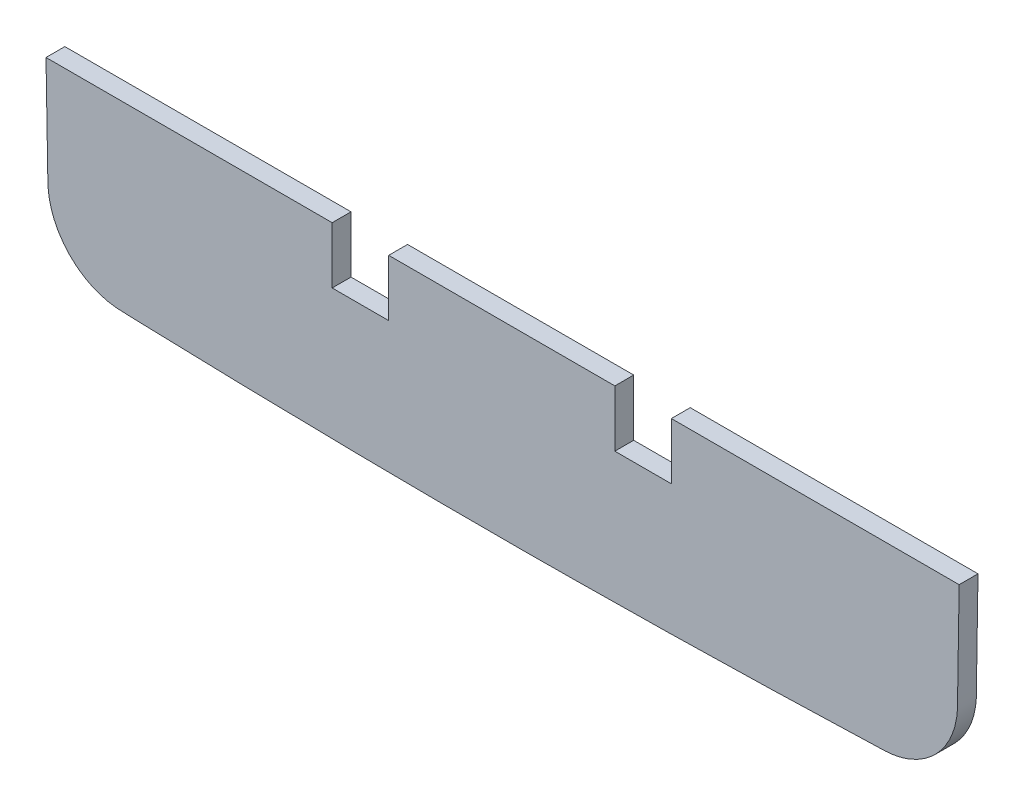
SolidWorks part; units mm, degrees
material "Balsa"
ref_plane "Front Plane" through (0, 0, 0) normal (0, 0, 1) x (1, 0, 0)
ref_plane "Top Plane" through (0, 0, 0) normal (0, 1, 0) x (1, 0, 0)
ref_plane "Right Plane" through (0, 0, 0) normal (1, 0, 0) x (0, 0, -1)
sketch "Sketch1" plane through (0, 0, 0) normal (0, 0, 1) x (1, 0, 0)
  line L0 (0, 0) -> (63.5, 0) construction
  line L1 (63.5, 0) -> (63.5, -63.8615) construction
  line L2 (63.5, 0) -> (63.5, 63.3303) construction
  line L3 (63.5, 0) -> (125.3812, 0) construction
  line L4 (1.8568, -38.4615) -> (125.1432, -38.4615)
  line L5 (48.26, -46.0815) -> (40.64, -38.4615) construction
  line L6 (78.74, -38.4615) -> (86.36, -38.4615)
  line L7 (78.74, -38.4615) -> (78.74, -46.0815)
  line L8 (78.74, -46.0815) -> (86.36, -46.0815)
  line L9 (86.36, -38.4615) -> (86.36, -46.0815)
  line L10 (78.74, -38.4615) -> (86.36, -46.0815) construction
  line L11 (78.74, -46.0815) -> (86.36, -38.4615) construction
  line L12 (48.26, -38.4615) -> (40.64, -46.0815) construction
  line L13 (40.64, -38.4615) -> (40.64, -46.0815)
  line L14 (48.26, -46.0815) -> (40.64, -46.0815)
  line L15 (48.26, -38.4615) -> (48.26, -46.0815)
  line L16 (48.26, -38.4615) -> (40.64, -38.4615)
  spline S0 degree 3 poles (54.6746, 63.3201) (72.3254, 63.3404) (81.6334, 63.261) (91.4786, 63.0757) (96.4012, 62.983) (101.4588, 62.8641) (106.6652, 62.7189) (109.2684, 62.6463) (111.9089, 62.5672) (114.589, 62.4817) (114.9241, 62.471) (115.2596, 62.4627) (115.9368, 62.4005) (116.2773, 62.3518) (116.6174, 62.2851) (117.2977, 62.1518) (117.9765, 61.9466) (119.2931, 61.385) (119.9309, 61.0284) (120.5286, 60.6045) (120.8274, 60.3925) (121.1162, 60.1638) (121.3925, 59.9193) (121.5306, 59.7971) (121.6656, 59.671) (121.8628, 59.4761) (121.9277, 59.4102) (122.0237, 59.3099) (122.0555, 59.2763) (122.1028, 59.2255) (122.1185, 59.2085) (122.142, 59.1829) (122.1498, 59.1744) (122.1615, 59.1615) (122.1654, 59.1573) (122.1732, 59.1487) (122.1779, 59.1435) (122.181, 59.1401) (122.9771, 58.2612) (123.6304, 57.2281) (124.5379, 55.0046) (124.7916, 53.8141) (124.8407, 52.6335) (124.8468, 52.4859) (124.8489, 52.3387) (124.8543, 52.0436) (124.8571, 51.8957) (124.8598, 51.7477) (124.8652, 51.4515) (124.8707, 51.1544) (124.8761, 50.8563) (124.8869, 50.2602) (124.8976, 49.66) (124.9083, 49.056) (124.9296, 47.8479) (124.9506, 46.624) (124.9711, 45.3844) (125.0123, 42.9053) (125.0517, 40.3631) (125.0888, 37.7579) (125.1074, 36.4553) (125.1253, 35.1369) (125.1426, 33.8028) (125.1513, 33.1357) (125.1598, 32.4647) (125.1681, 31.7898) (125.1722, 31.4523) (125.1763, 31.1138) (125.1804, 30.7744) (125.1824, 30.6047) (125.1844, 30.4347) (125.1875, 30.1794) (125.1885, 30.0942) (125.1899, 29.9664) (125.1904, 29.9237) (125.1912, 29.8598) (125.1914, 29.8384) (125.1918, 29.8064) (125.1919, 29.7958) (125.1921, 29.7798) (125.1922, 29.7744) (125.1923, 29.7638) (125.1924, 29.7566) (125.1924, 29.7531) (125.2344, 26.1435) (125.2782, 21.8295) (125.3138, 16.8106) (125.3316, 14.3012) (125.3473, 11.6156) (125.3591, 8.7538) (125.3651, 7.3229) (125.37, 5.848) (125.3738, 4.3291) (125.3757, 3.5696) (125.3773, 2.7992) (125.3786, 2.0177) (125.3793, 1.627) (125.3798, 1.2335) (125.3803, 0.8373) (125.3805, 0.6391) (125.3807, 0.4403) (125.381, 0.1411) (125.3811, 0.0412) (125.3813, -0.1089) (125.3813, -0.159) (125.3814, -0.2342) (125.3814, -0.2593) (125.3814, -0.2969) (125.3814, -0.3095) (125.3814, -0.3346) (125.3814, -0.3459) (125.3815, -0.3597) (125.3867, -7.4209) (125.3638, -13.4611) (125.3337, -18.4799) (125.3187, -20.9893) (125.3018, -23.2434) (125.2849, -25.2423) (125.2765, -26.2418) (125.2681, -27.1774) (125.2599, -28.0493) (125.2558, -28.4852) (125.2517, -28.9052) (125.2477, -29.3092) (125.2457, -29.5113) (125.2438, -29.7093) (125.2408, -30.0004) (125.2399, -30.0964) (125.2384, -30.239) (125.2379, -30.2862) (125.2372, -30.3568) (125.237, -30.3802) (125.2366, -30.4153) (125.2365, -30.427) (125.2363, -30.4445) (125.2362, -30.4503) (125.2362, -30.459) (125.2361, -30.4619) (125.2361, -30.4663) (125.2361, -30.4678) (125.236, -30.4707) (125.236, -30.4709) (125.236, -30.4736) (125.179, -36.029) (125.1091, -41.2841) (125.0327, -46.2395) (125.0136, -47.4783) (124.9941, -48.6984) (124.9743, -49.8998) (124.9644, -50.5005) (124.9544, -51.0965) (124.9443, -51.6878) (124.9393, -51.9835) (124.9342, -52.2779) (124.9291, -52.5713) (124.9266, -52.7179) (124.9247, -52.8642) (124.9129, -53.1574) (124.9038, -53.3041) (124.8916, -53.4507) (124.7938, -54.6239) (124.4947, -55.7922) (124.0038, -56.8717) (123.7584, -57.4114) (123.4662, -57.9292) (123.1347, -58.416) (122.969, -58.6594) (122.7933, -58.8951) (122.6087, -59.1219) (122.5164, -59.2354) (122.4219, -59.3466) (122.2769, -59.51) (122.228, -59.5638) (122.1539, -59.6438) (122.129, -59.6703) (122.0916, -59.7098) (122.0791, -59.7229) (122.0603, -59.7426) (122.054, -59.7491) (122.0446, -59.7589) (122.0414, -59.7621) (122.0351, -59.7687) (122.0329, -59.771) (122.0288, -59.7752) (120.9867, -60.8512) (119.7112, -61.6814) (118.3671, -62.1967) (117.6951, -62.4544) (117.0057, -62.6355) (116.3186, -62.7439) (115.975, -62.7981) (115.632, -62.8341) (115.2919, -62.8524) (115.1218, -62.8615) (114.9526, -62.866) (114.6141, -62.8777) (114.445, -62.8836) (114.276, -62.8894) (111.5731, -62.9828) (108.9135, -63.0695) (106.2945, -63.1494) (101.0567, -63.3091) (95.9813, -63.4414) (86.1268, -63.6511) (81.3478, -63.7286) (76.7076, -63.7803) (74.3874, -63.8062) (72.102, -63.8257) (69.8505, -63.8391) (68.7248, -63.8459) (67.6075, -63.8511) (65.3896, -63.8586) (64.2876, -63.8609) (63.1969, -63.8617) (54.4717, -63.8687) (45.2104, -63.7853) (35.3493, -63.5924) (30.4187, -63.496) (25.3375, -63.3725) (20.091, -63.222) (18.7794, -63.1844) (17.4574, -63.1451) (16.1247, -63.1042) (15.4584, -63.0837) (14.7894, -63.0628) (14.1177, -63.0415) (13.7818, -63.0309) (13.4453, -63.0201) (12.7708, -62.9984) (12.4333, -62.9897) (12.0943, -62.9762) (10.7385, -62.922) (9.3303, -62.5848) (8.0249, -61.938) (7.3723, -61.6146) (6.7455, -61.216) (6.1651, -60.7512) (5.8749, -60.5187) (5.5963, -60.2697) (5.332, -60.0053) (5.1999, -59.8731) (5.0713, -59.737) (4.8841, -59.5275) (4.8226, -59.4568) (4.7319, -59.3494) (4.7019, -59.3134) (4.6572, -59.2591) (4.6424, -59.2409) (4.6203, -59.2136) (4.6129, -59.2045) (4.6019, -59.1908) (4.5982, -59.1862) (4.5909, -59.1771) (4.5864, -59.1714) (4.5836, -59.1679) (3.8629, -58.266) (3.2834, -57.2273) (2.8987, -56.1215) (2.7064, -55.5687) (2.5615, -54.9992) (2.4651, -54.4232) (2.4169, -54.1353) (2.3809, -53.8457) (2.357, -53.5559) (2.3451, -53.411) (2.3363, -53.266) (2.3248, -52.9763) (2.3228, -52.8317) (2.3199, -52.6867) (2.2745, -50.3665) (2.2299, -47.9702) (2.1436, -43.0251) (2.102, -40.4763) (2.0626, -37.8512) (2.0429, -36.5387) (2.0238, -35.2071) (2.0053, -33.8564) (1.9961, -33.1811) (1.987, -32.501) (1.9782, -31.8161) (1.9737, -31.4736) (1.9693, -31.13) (1.965, -30.7852) (1.9628, -30.6128) (1.9606, -30.4401) (1.9574, -30.1805) (1.9563, -30.094) (1.9547, -29.964) (1.9542, -29.9206) (1.9534, -29.8556) (1.9531, -29.8339) (1.9527, -29.8014) (1.9526, -29.7905) (1.9524, -29.7742) (1.9523, -29.7688) (1.9522, -29.7607) (1.9522, -29.758) (1.9521, -29.7525) (1.9521, -29.7485) (1.952, -29.7471) (1.9172, -26.9027) (1.8728, -22.994) (1.8326, -18.0199) (1.8126, -15.5328) (1.7937, -12.7794) (1.7786, -9.7596) (1.771, -8.2497) (1.7644, -6.6732) (1.7591, -5.0301) (1.7564, -4.2086) (1.7541, -3.3704) (1.7521, -2.5156) (1.7511, -2.0882) (1.7502, -1.6566) (1.7494, -1.2209) (1.749, -1.003) (1.7487, -0.7841) (1.7483, -0.5642) (1.7481, -0.4542) (1.748, -0.344) (1.7477, -0.1782) (1.7477, -0.1229) (1.7475, -0.0398) (1.7475, -0.0121) (1.7474, 0.0295) (1.7474, 0.0433) (1.7474, 0.0711) (1.7474, 0.0865) (1.7474, 0.0988) (1.739, 6.4209) (1.7537, 12.0696) (1.7782, 17.0439) (1.7905, 19.5311) (1.8052, 21.8497) (1.8211, 23.9998) (1.8291, 25.0748) (1.8373, 26.1077) (1.8457, 27.0985) (1.8499, 27.5939) (1.8542, 28.0787) (1.8584, 28.5531) (1.8605, 28.7902) (1.8627, 29.0247) (1.8648, 29.2566) (1.8659, 29.3726) (1.8669, 29.4879) (1.8685, 29.6598) (1.8691, 29.717) (1.8699, 29.8025) (1.8701, 29.8309) (1.8705, 29.8735) (1.8707, 29.8877) (1.8709, 29.909) (1.8709, 29.9161) (1.871, 29.9267) (1.8711, 29.9303) (1.8711, 29.9374) (1.8712, 29.9392) (1.8712, 29.9444) (1.9224, 35.3651) (1.986, 40.5382) (2.0566, 45.4638) (2.0743, 46.6952) (2.0924, 47.9112) (2.1109, 49.1117) (2.1202, 49.7119) (2.1295, 50.3083) (2.1389, 50.9008) (2.1436, 51.1971) (2.1484, 51.4924) (2.1579, 52.081) (2.1591, 52.374) (2.1757, 52.668) (2.242, 53.8441) (2.5108, 55.0258) (2.9778, 56.1266) (3.2113, 56.677) (3.4937, 57.2074) (3.818, 57.708) (3.9801, 57.9583) (4.1527, 58.2012) (4.3349, 58.4355) (4.426, 58.5527) (4.5195, 58.6677) (4.6631, 58.8368) (4.7116, 58.8926) (4.7852, 58.9755) (4.8098, 59.0029) (4.847, 59.0439) (4.8594, 59.0575) (4.8781, 59.0779) (4.8844, 59.0847) (4.8938, 59.0949) (4.8969, 59.0982) (4.9031, 59.105) (4.9055, 59.1075) (4.9094, 59.1118) (5.9147, 60.1951) (7.1549, 61.0446) (8.4723, 61.5897) (9.131, 61.8622) (9.8091, 62.0599) (10.4877, 62.1861) (10.8271, 62.2492) (11.1665, 62.2944) (11.8412, 62.3501) (12.1755, 62.3568) (12.5096, 62.3682) (15.1828, 62.4595) (17.8166, 62.5443) (20.4132, 62.6226) (25.6066, 62.7791) (30.6521, 62.9091) (35.5634, 63.0126) (45.3861, 63.2197) (54.6746, 63.3201) (72.3254, 63.3404) (81.6334, 63.261) knots -0.006135 -0.006135 0 0 0.006135 0.006135 0.006135 0.01227 0.01227 0.01227 0.018405 0.018405 0.018405 0.02454 0.02454 0.030675 0.030675 0.030675 0.03681 0.03681 0.042945 0.042945 0.042945 0.04908 0.04908 0.04908 0.055215 0.055215 0.06135 0.06135 0.067485 0.067485 0.07362 0.07362 0.079755 0.079755 0.08589 0.08589 0.092025 0.092025 0.092025 0.09816 0.09816 0.104294 0.104294 0.104294 0.110429 0.110429 0.116564 0.116564 0.116564 0.122699 0.122699 0.122699 0.128834 0.128834 0.128834 0.134969 0.134969 0.134969 0.141104 0.141104 0.141104 0.147239 0.147239 0.147239 0.153374 0.153374 0.153374 0.159509 0.159509 0.159509 0.165644 0.165644 0.171779 0.171779 0.177914 0.177914 0.184049 0.184049 0.190184 0.190184 0.196319 0.196319 0.202454 0.202454 0.202454 0.208589 0.208589 0.208589 0.214724 0.214724 0.214724 0.220859 0.220859 0.220859 0.226994 0.226994 0.226994 0.233129 0.233129 0.233129 0.239264 0.239264 0.245399 0.245399 0.251534 0.251534 0.257669 0.257669 0.263804 0.263804 0.269939 0.269939 0.269939 0.276074 0.276074 0.276074 0.282209 0.282209 0.282209 0.288344 0.288344 0.288344 0.294479 0.294479 0.294479 0.300613 0.300613 0.306748 0.306748 0.312883 0.312883 0.319018 0.319018 0.325153 0.325153 0.331288 0.331288 0.337423 0.337423 0.343558 0.343558 0.349693 0.349693 0.349693 0.355828 0.355828 0.355828 0.361963 0.361963 0.361963 0.368098 0.368098 0.368098 0.374233 0.374233 0.374233 0.380368 0.380368 0.386503 0.386503 0.386503 0.392638 0.392638 0.392638 0.398773 0.398773 0.398773 0.404908 0.404908 0.404908 0.411043 0.411043 0.417178 0.417178 0.423313 0.423313 0.429448 0.429448 0.435583 0.435583 0.441718 0.441718 0.447853 0.447853 0.447853 0.453988 0.453988 0.453988 0.460123 0.460123 0.460123 0.466258 0.466258 0.466258 0.472393 0.472393 0.478528 0.478528 0.478528 0.484663 0.484663 0.484663 0.490798 0.490798 0.496933 0.496933 0.496933 0.503067 0.503067 0.503067 0.509202 0.509202 0.515337 0.515337 0.515337 0.521472 0.521472 0.521472 0.527607 0.527607 0.527607 0.533742 0.533742 0.533742 0.539877 0.539877 0.539877 0.546012 0.546012 0.552147 0.552147 0.552147 0.558282 0.558282 0.558282 0.564417 0.564417 0.564417 0.570552 0.570552 0.570552 0.576687 0.576687 0.582822 0.582822 0.588957 0.588957 0.595092 0.595092 0.601227 0.601227 0.607362 0.607362 0.613497 0.613497 0.613497 0.619632 0.619632 0.619632 0.625767 0.625767 0.625767 0.631902 0.631902 0.631902 0.638037 0.638037 0.644172 0.644172 0.644172 0.650307 0.650307 0.656442 0.656442 0.656442 0.662577 0.662577 0.662577 0.668712 0.668712 0.668712 0.674847 0.674847 0.674847 0.680982 0.680982 0.687117 0.687117 0.693252 0.693252 0.699387 0.699387 0.705521 0.705521 0.711656 0.711656 0.717791 0.717791 0.723926 0.723926 0.723926 0.730061 0.730061 0.730061 0.736196 0.736196 0.736196 0.742331 0.742331 0.742331 0.748466 0.748466 0.748466 0.754601 0.754601 0.754601 0.760736 0.760736 0.760736 0.766871 0.766871 0.773006 0.773006 0.779141 0.779141 0.785276 0.785276 0.791411 0.791411 0.791411 0.797546 0.797546 0.797546 0.803681 0.803681 0.803681 0.809816 0.809816 0.809816 0.815951 0.815951 0.815951 0.822086 0.822086 0.822086 0.828221 0.828221 0.834356 0.834356 0.840491 0.840491 0.846626 0.846626 0.852761 0.852761 0.858896 0.858896 0.865031 0.865031 0.865031 0.871166 0.871166 0.871166 0.877301 0.877301 0.877301 0.883436 0.883436 0.883436 0.889571 0.889571 0.895706 0.895706 0.895706 0.90184 0.90184 0.90184 0.907975 0.907975 0.907975 0.91411 0.91411 0.91411 0.920245 0.920245 0.92638 0.92638 0.932515 0.932515 0.93865 0.93865 0.944785 0.944785 0.95092 0.95092 0.957055 0.957055 0.957055 0.96319 0.96319 0.96319 0.969325 0.969325 0.969325 0.97546 0.97546 0.981595 0.981595 0.981595 0.98773 0.98773 0.98773 0.993865 0.993865 0.993865 1 1 1.006135 1.006135 1.006135 only from (63.5, 63.3303) to (63.5, 63.3303)
  point P4 (1.7475, 0)
  point P11 (82.55, -42.2715)
  point P17 (63.5, -38.4615)
  point P19 (44.45, -42.2715)
  dimension "D1" = 63.5
  dimension "D2" = 61.7525
  dimension "D3" = 63.3303
  dimension "D4" = 63.8615
  dimension "D5" = 38.4615
  dimension "D6" = 15.24
  dimension "D7" = 7.62
  dimension "D8" = 7.62
extrude "Boss-Extrude1" add sketch "Sketch1" along normal blind 2.54 contours S0 L4 L9 L8 L7 L15 L14 L13 region at (63.6889, -50.883, 0)
